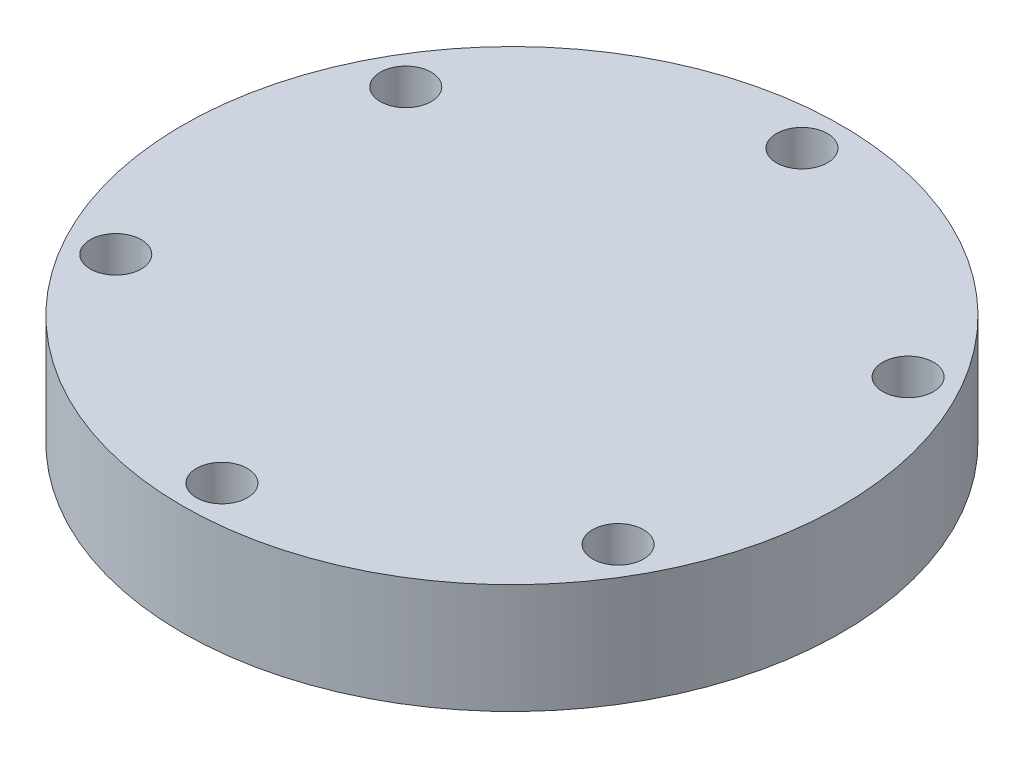
SolidWorks part; units mm, degrees
material "Copper"
ref_plane "Front Plane" through (0, 0, 0) normal (0, 0, 1) x (1, 0, 0)
ref_plane "Top Plane" through (0, 0, 0) normal (0, 1, 0) x (1, 0, 0)
ref_plane "Right Plane" through (0, 0, 0) normal (1, 0, 0) x (0, 0, -1)
ref_axis "Y Axis" through (0, 6.6675, 0) along (0, -1, 0)
sketch "outer" plane through (0, 0, 0) normal (0, 1, 0) x (1, 0, 0)
  circle A0 centre (0, 0) radius 19.05
  dimension "D1" = 38.1
extrude "Body" add sketch "outer" along normal blind 6.35
sketch "inner" plane through (0, 0, 0) normal (0, 1, 0) x (1, 0, 0)
  circle A0 centre (0, 0) radius 11.938
  dimension "D1" = 23.876
extrude "Pocket" cut sketch "inner" along normal blind 3.81
sketch "Screw Position" plane through (0, 0, 0) normal (0, 1, 0) x (1, 0, 0)
  point P0 (0, 16.764)
  dimension "D1" = 16.764
hole_wizard "#4 Clearance Hole1" positions "Sketch7" profile "Sketch8" hole size "#4" standard "ANSI Inch" end condition through all
sketch "Sketch7" plane through (0, 6.35, 0) normal (0, 1, 0) x (1, 0, 0)
  point P0 (0, 16.764)
sketch "Sketch8" plane through (0, 6.35, -16.764) normal (1, 0, 0) x (0, 0, 1)
  line L0 (0, 0) -> (0, 6.35)
  line L1 (0, 6.35) -> (1.4732, 6.35)
  line L2 (1.4732, 6.35) -> (1.4732, 0)
  line L5 (1.4732, 0) -> (0, 0)
  line L11 (0, -6.35) -> (0, 107.95) construction
  dimension "Thru Hole Dia." = 2.9464
  dimension "Thru Hole Depth" = 6.35
pattern_circular "Screw Holes" count 6 over 360 about axis through (0, 6.6675, 0) along (0, -1, 0) of "#4 Clearance Hole1"
sketch "Post Sketch" plane through (0, 0, 0) normal (0, 1, 0) x (1, 0, 0)
  circle A0 centre (0, -7) radius 1.2065
  circle A1 centre (5.3033, -5.3033) radius 1.2065
  point P0 (0, -7)
  point P1 (5.3033, -5.3033)
  dimension "D3" = 2.413
  dimension "D4" = 2.413
  dimension "D1" = 7
  dimension "D2" = 7.5
extrude "Post" add sketch "Post Sketch" against normal blind 4.572 from surface starting at face at (0, 3.81, 11.938)
pattern_circular "CirPattern1" count 4 over 360 about axis through (0, 6.6675, 0) along (0, -1, 0) of "Post"
equation "\"outer_d\"= 3 / 2in"
equation "\"top_h\"= 1 / 4in"
equation "\"screw_r\"= 0.66in"
equation "\"inner_d\"= 0.94in"
equation "\"inner_h\"= 150mil"
equation "\"D1@outer\" = \"outer_d\""
equation "\"D1@Body\" = \"top_h\""
equation "\"D1@inner\"=\"inner_d\""
equation "\"D1@Pocket\" = \"inner_h\""
equation "\"D1@Screw Position\"=\"screw_r\""
equation "\"post_r1\"= 7mm"
equation "\"post_r2\"= 7.5mm"
equation "\"post_bottom_h\"= 0.03in"
equation "\"D1@Post Sketch\" = \"post_r1\""
equation "\"D2@Post Sketch\" = \"post_r2\""
equation "\"post_d\"= 0.095in"
equation "\"D3@Post Sketch\"=\"post_d\""
equation "\"D4@Post Sketch\"=\"post_d\""
equation "\"D1@Post\" = \"inner_h\" + \"post_bottom_h\""
